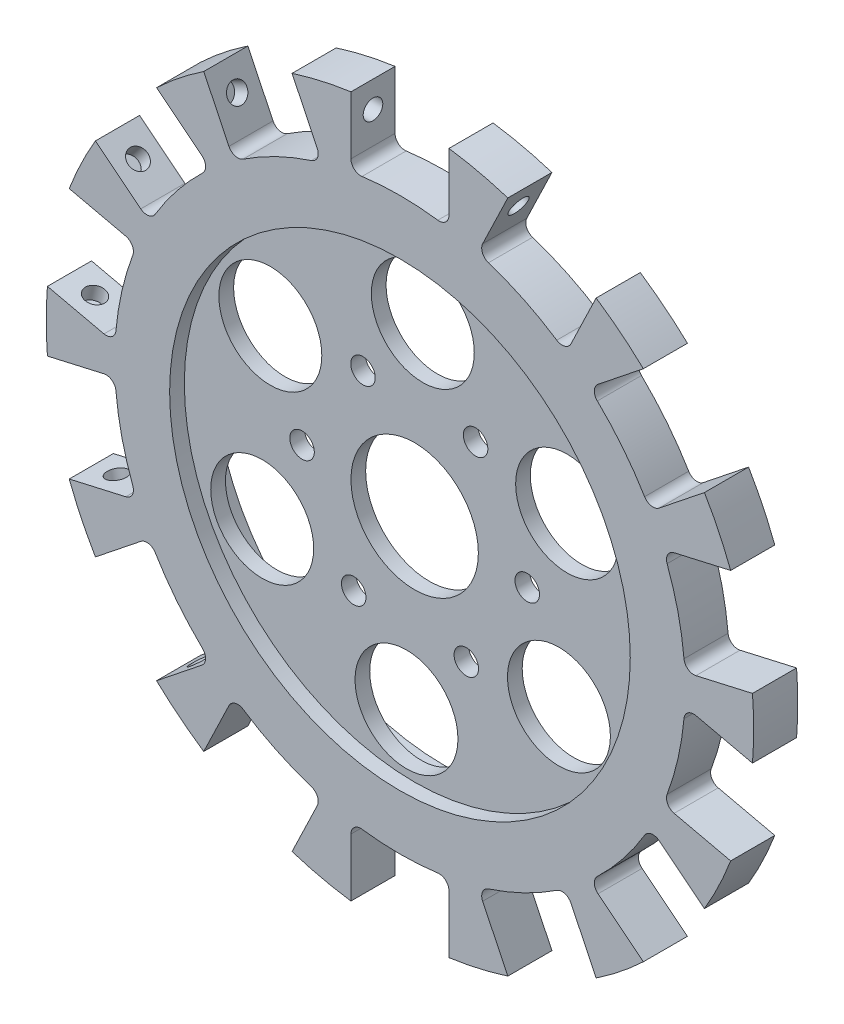
SolidWorks part; units mm, degrees
material "AISI 1020 钢，冷轧"
ref_plane "前视基准面" through (0, 0, 0) normal (0, 0, 1) x (1, 0, 0)
ref_plane "上视基准面" through (0, 0, 0) normal (0, 1, 0) x (1, 0, 0)
ref_plane "右视基准面" through (0, 0, 0) normal (1, 0, 0) x (0, 0, -1)
sketch "草图1" plane through (0, 0, 0) normal (0, 0, 1) x (1, 0, 0)
  circle A0 centre (0, 0) radius 72.2
  dimension "D1" = 144.4
extrude "凸台-拉伸1" add sketch "草图1" along normal blind 9
sketch "草图2" plane through (0, 0, 9) normal (0, 0, 1) x (1, 0, 0)
  line L0 (0, 72.2) -> (0, -72.2) construction
  line L1 (-10, 71.5041) -> (-10, 59.6661)
  line L2 (10, 71.5041) -> (10, 59.6661)
  line L3 (22.0148, 68.7618) -> (16.8784, 58.0961)
  line L4 (40.0342, 60.0842) -> (34.8978, 49.4184)
  line L5 (-10, 72.2) -> (-10, -72.2) construction
  line L6 (49.6693, 52.4004) -> (40.4139, 45.0195)
  line L7 (10, 72.2) -> (10, -72.2) construction
  line L8 (62.1391, 36.7638) -> (52.8837, 29.3829)
  line L9 (67.4862, 25.6604) -> (55.9449, 23.0262)
  line L10 (71.9366, 6.1619) -> (60.3953, 3.5277)
  line L11 (71.9366, -6.1619) -> (60.3953, -3.5277)
  line L12 (67.4862, -25.6604) -> (55.9449, -23.0262)
  line L13 (62.1391, -36.7638) -> (52.8837, -29.3829)
  line L14 (49.6693, -52.4004) -> (40.4139, -45.0195)
  line L15 (40.0342, -60.0842) -> (34.8978, -49.4184)
  line L16 (22.0148, -68.7618) -> (16.8784, -58.0961)
  line L17 (10, -71.5041) -> (10, -59.6661)
  line L18 (-10, -71.5041) -> (-10, -59.6661)
  line L19 (-22.0148, -68.7618) -> (-16.8784, -58.0961)
  line L20 (-40.0342, -60.0842) -> (-34.8978, -49.4184)
  line L21 (-49.6693, -52.4004) -> (-40.4139, -45.0195)
  line L22 (-62.1391, -36.7638) -> (-52.8837, -29.3829)
  line L23 (-67.4862, -25.6604) -> (-55.9449, -23.0262)
  line L24 (-71.9366, -6.1619) -> (-60.3953, -3.5277)
  line L25 (-71.9366, 6.1619) -> (-60.3953, 3.5277)
  line L26 (-67.4862, 25.6604) -> (-55.9449, 23.0262)
  line L27 (-62.1391, 36.7638) -> (-52.8837, 29.3829)
  line L28 (-49.6693, 52.4004) -> (-40.4139, 45.0195)
  line L29 (-40.0342, 60.0842) -> (-34.8978, 49.4184)
  line L30 (-22.0148, 68.7618) -> (-16.8784, 58.0961)
  arc A0 (7.7342, 57.6838) -> (-7.7342, 57.6838) centre (0, 0) ccw
  circle A1 centre (0, 0) radius 72.2 construction
  arc A2 (10, 71.5041) -> (-10, 71.5041) centre (0, 0) ccw
  arc A3 (7.7342, 57.6838) -> (10, 59.6661) centre (8, 59.6661) ccw
  arc A4 (-7.7342, 57.6838) -> (-10, 59.6661) centre (-8, 59.6661) cw
  arc A5 (31.9964, 48.6156) -> (18.0598, 55.3271) centre (0, 0) ccw
  arc A6 (40.0342, 60.0842) -> (22.0148, 68.7618) centre (0, 0) ccw
  arc A7 (31.9964, 48.6156) -> (34.8978, 49.4184) centre (33.0959, 50.2862) ccw
  arc A8 (18.0598, 55.3271) -> (16.8784, 58.0961) centre (18.6804, 57.2283) cw
  arc A9 (49.9212, 29.9184) -> (40.2768, 42.0121) centre (0, 0) ccw
  arc A10 (62.1391, 36.7638) -> (49.6693, 52.4004) centre (0, 0) ccw
  arc A11 (49.9212, 29.9184) -> (52.8837, 29.3829) centre (51.6367, 30.9465) ccw
  arc A12 (40.2768, 42.0121) -> (40.4139, 45.0195) centre (41.6609, 43.4558) cw
  arc A13 (57.9586, 5.2955) -> (54.5165, 20.3762) centre (0, 0) ccw
  arc A14 (71.9366, 6.1619) -> (67.4862, 25.6604) centre (0, 0) ccw
  arc A15 (57.9586, 5.2955) -> (60.3953, 3.5277) centre (59.9503, 5.4775) ccw
  arc A16 (54.5165, 20.3762) -> (55.9449, 23.0262) centre (56.39, 21.0764) cw
  arc A17 (54.5165, -20.3762) -> (57.9586, -5.2955) centre (0, 0) ccw
  arc A18 (67.4862, -25.6604) -> (71.9366, -6.1619) centre (0, 0) ccw
  arc A19 (54.5165, -20.3762) -> (55.9449, -23.0262) centre (56.39, -21.0764) ccw
  arc A20 (57.9586, -5.2955) -> (60.3953, -3.5277) centre (59.9503, -5.4775) cw
  arc A21 (40.2768, -42.0121) -> (49.9212, -29.9184) centre (0, 0) ccw
  arc A22 (49.6693, -52.4004) -> (62.1391, -36.7638) centre (0, 0) ccw
  arc A23 (40.2768, -42.0121) -> (40.4139, -45.0195) centre (41.6609, -43.4558) ccw
  arc A24 (49.9212, -29.9184) -> (52.8837, -29.3829) centre (51.6367, -30.9465) cw
  arc A25 (18.0598, -55.3271) -> (31.9964, -48.6156) centre (0, 0) ccw
  arc A26 (22.0148, -68.7618) -> (40.0342, -60.0842) centre (0, 0) ccw
  arc A27 (18.0598, -55.3271) -> (16.8784, -58.0961) centre (18.6804, -57.2283) ccw
  arc A28 (31.9964, -48.6156) -> (34.8978, -49.4184) centre (33.0959, -50.2862) cw
  arc A29 (-7.7342, -57.6838) -> (7.7342, -57.6838) centre (0, 0) ccw
  arc A30 (-10, -71.5041) -> (10, -71.5041) centre (0, 0) ccw
  arc A31 (-7.7342, -57.6838) -> (-10, -59.6661) centre (-8, -59.6661) ccw
  arc A32 (7.7342, -57.6838) -> (10, -59.6661) centre (8, -59.6661) cw
  arc A33 (-31.9964, -48.6156) -> (-18.0598, -55.3271) centre (0, 0) ccw
  arc A34 (-40.0342, -60.0842) -> (-22.0148, -68.7618) centre (0, 0) ccw
  arc A35 (-31.9964, -48.6156) -> (-34.8978, -49.4184) centre (-33.0959, -50.2862) ccw
  arc A36 (-18.0598, -55.3271) -> (-16.8784, -58.0961) centre (-18.6804, -57.2283) cw
  arc A37 (-49.9212, -29.9184) -> (-40.2768, -42.0121) centre (0, 0) ccw
  arc A38 (-62.1391, -36.7638) -> (-49.6693, -52.4004) centre (0, 0) ccw
  arc A39 (-49.9212, -29.9184) -> (-52.8837, -29.3829) centre (-51.6367, -30.9465) ccw
  arc A40 (-40.2768, -42.0121) -> (-40.4139, -45.0195) centre (-41.6609, -43.4558) cw
  arc A41 (-57.9586, -5.2955) -> (-54.5165, -20.3762) centre (0, 0) ccw
  arc A42 (-71.9366, -6.1619) -> (-67.4862, -25.6604) centre (0, 0) ccw
  arc A43 (-57.9586, -5.2955) -> (-60.3953, -3.5277) centre (-59.9503, -5.4775) ccw
  arc A44 (-54.5165, -20.3762) -> (-55.9449, -23.0262) centre (-56.39, -21.0764) cw
  arc A45 (-54.5165, 20.3762) -> (-57.9586, 5.2955) centre (0, 0) ccw
  arc A46 (-67.4862, 25.6604) -> (-71.9366, 6.1619) centre (0, 0) ccw
  arc A47 (-54.5165, 20.3762) -> (-55.9449, 23.0262) centre (-56.39, 21.0764) ccw
  arc A48 (-57.9586, 5.2955) -> (-60.3953, 3.5277) centre (-59.9503, 5.4775) cw
  arc A49 (-40.2768, 42.0121) -> (-49.9212, 29.9184) centre (0, 0) ccw
  arc A50 (-49.6693, 52.4004) -> (-62.1391, 36.7638) centre (0, 0) ccw
  arc A51 (-40.2768, 42.0121) -> (-40.4139, 45.0195) centre (-41.6609, 43.4558) ccw
  arc A52 (-49.9212, 29.9184) -> (-52.8837, 29.3829) centre (-51.6367, 30.9465) cw
  arc A53 (-18.0598, 55.3271) -> (-31.9964, 48.6156) centre (0, 0) ccw
  arc A54 (-22.0148, 68.7618) -> (-40.0342, 60.0842) centre (0, 0) ccw
  arc A55 (-18.0598, 55.3271) -> (-16.8784, 58.0961) centre (-18.6804, 57.2283) ccw
  arc A56 (-31.9964, 48.6156) -> (-34.8978, 49.4184) centre (-33.0959, 50.2862) cw
  point P125 (0, 0)
  dimension "D1" = 14
  dimension "D4" = 2
  dimension "D2" = 10
  dimension "D3" = 10
  dimension "D5" = 14
extrude "切除-拉伸2" cut sketch "草图2" against normal blind 9
sketch "草图3" plane through (0, 0, 9) normal (0, 0, 1) x (1, 0, 0)
  circle A0 centre (0, 0) radius 47
  dimension "D1" = 94
extrude "切除-拉伸3" cut sketch "草图3" against normal blind 3
sketch "草图4" plane through (0, 0, 0) normal (0, 0, -1) x (-1, 0, 0)
  circle A0 centre (0, 0) radius 47
  dimension "D1" = 94
extrude "切除-拉伸4" cut sketch "草图4" against normal blind 3
sketch "草图5" plane through (0, 0, 3) normal (0, 0, -1) x (-1, 0, 0)
  line L0 (0, 0) -> (10.5392, 20.4432) construction
  line L2 (0, 0) -> (-1.6654, 34.9604) construction
  line L3 (-31.4653, 48.961) -> (0, 0) construction
  circle A0 centre (0, 0) radius 13
  circle A1 centre (0, 0) radius 23 construction
  circle A2 centre (-12.4347, 19.3488) radius 2.5
  circle A3 centre (10.5392, 20.4432) radius 2.5
  circle A4 centre (29.4439, 18.9224) radius 10.5
  circle A5 centre (22.9739, 1.0944) radius 2.5
  circle A6 centre (31.1092, -16.0379) radius 10.5
  circle A7 centre (12.4347, -19.3488) radius 2.5
  circle A8 centre (0, 0) radius 35 construction
  circle A9 centre (-1.6654, 34.9604) radius 10.5
  circle A10 centre (1.6654, -34.9604) radius 10.5
  circle A11 centre (-10.5392, -20.4432) radius 2.5
  circle A12 centre (-29.4439, -18.9224) radius 10.5
  circle A13 centre (-22.9739, -1.0944) radius 2.5
  circle A14 centre (-31.1092, 16.0379) radius 10.5
  circle A15 centre (0, 0) radius 47 construction
  arc A16 (-18.0598, 55.3271) -> (-31.9964, 48.6156) centre (0, 0) ccw construction
  dimension "D1" = 5
  dimension "D2" = 46
  dimension "D3" = 30
  dimension "D5" = 70
  dimension "D6" = 30
  dimension "D7" = 21
  dimension "D4" = 6
sketch "草图6" plane through (-10, 0, 0) normal (1, 0, 0) x (0, 0, -1)
  line L0 (0, 71.5041) -> (-9, 71.5041) construction
  line L1 (0, 71.5041) -> (0, 59.6661) construction
  circle A0 centre (-4.5, 66.1541) radius 2
  dimension "D1" = 4
  dimension "D2" = 5.35
  dimension "D3" = 4.5
extrude "切除-拉伸6" cut sketch "草图6" against normal blind 3
extrude "切除-拉伸7" cut sketch "草图5" against normal through all contours A9 | A14 | A2 | A4 | A6 | A5 | A7 | A10 | A11 | A12 | A13 | A3 | A0 | A3 region at (0, 0, 3) region at (12.4347, 19.3488, 3) region at (-10.5392, 20.4432, 3) region at (-29.4439, 18.9224, 3) region at (-22.9739, 1.0944, 3) region at (-31.1092, -16.0379, 3) region at (-12.4347, -19.3488, 3) region at (1.6654, 34.9604, 3) region at (-1.6654, -34.9604, 3) region at (10.5392, -20.4432, 3) region at (29.4439, -18.9224, 3) region at (22.9739, -1.0944, 3) region at (31.1092, 16.0379, 3)
pattern_circular "阵列(圆周)1" count 14 over 360 about axis through (0, 0, 9) along (0, 0, -1) of "切除-拉伸6"
